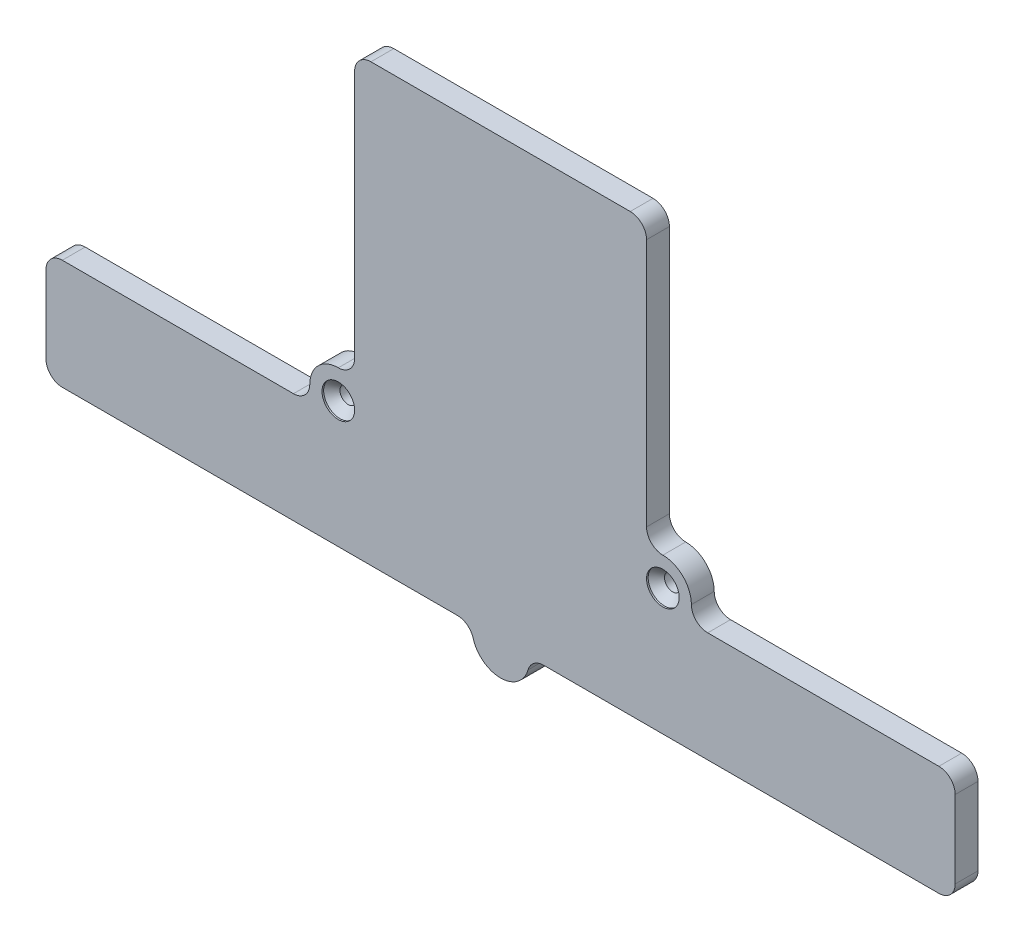
SolidWorks part; units mm, degrees
ref_plane "Front Plane" through (0, 0, 0) normal (0, 0, 1) x (1, 0, 0)
ref_plane "Top Plane" through (0, 0, 0) normal (0, 1, 0) x (1, 0, 0)
ref_plane "Right Plane" through (0, 0, 0) normal (1, 0, 0) x (0, 0, -1)
sketch "Sketch1" plane through (0, 0, 0) normal (0, 0, 1) x (1, 0, 0)
  line L8 (-53.75, -26.75) -> (-5.2915, -26.75)
  line L9 (55.75, -24.75) -> (55.75, -15.25)
  line L10 (53.75, -13.25) -> (25.4, -13.25)
  line L11 (17.9, -5.75) -> (17.9, 24.75)
  line L12 (15.9, 26.75) -> (-15.9, 26.75)
  line L13 (-17.9, 24.75) -> (-17.9, -5.75)
  line L14 (-25.4, -13.25) -> (-53.75, -13.25)
  line L15 (-55.75, -15.25) -> (-55.75, -24.75)
  line L16 (-53.75, -26.75) -> (-5.2915, -26.75)
  line L17 (55.75, -24.75) -> (55.75, -15.25)
  line L18 (53.75, -13.25) -> (25.4, -13.25)
  line L19 (17.9, -5.75) -> (17.9, 24.75)
  line L20 (15.9, 26.75) -> (-15.9, 26.75)
  line L21 (-17.9, 24.75) -> (-17.9, -5.75)
  line L22 (-25.4, -13.25) -> (-53.75, -13.25)
  line L23 (-55.75, -15.25) -> (-55.75, -24.75)
  line L66 (5.2915, -26.75) -> (53.75, -26.75)
  line L67 (5.2915, -26.75) -> (53.75, -26.75)
  arc A12 (53.75, -26.75) -> (55.75, -24.75) centre (53.75, -24.75) ccw
  arc A13 (55.75, -15.25) -> (53.75, -13.25) centre (53.75, -15.25) ccw
  arc A14 (23.4, -11.25) -> (25.4, -13.25) centre (25.4, -11.25) ccw
  arc A15 (23.4, -11.25) -> (19.9, -7.75) centre (19.9, -11.25) ccw
  arc A16 (17.9, -5.75) -> (19.9, -7.75) centre (19.9, -5.75) ccw
  arc A17 (17.9, 24.75) -> (15.9, 26.75) centre (15.9, 24.75) ccw
  arc A18 (-15.9, 26.75) -> (-17.9, 24.75) centre (-15.9, 24.75) ccw
  arc A19 (-19.9, -7.75) -> (-17.9, -5.75) centre (-19.9, -5.75) ccw
  arc A20 (-19.9, -7.75) -> (-23.4, -11.25) centre (-19.9, -11.25) ccw
  arc A21 (-25.4, -13.25) -> (-23.4, -11.25) centre (-25.4, -11.25) ccw
  arc A22 (-53.75, -13.25) -> (-55.75, -15.25) centre (-53.75, -15.25) ccw
  arc A23 (-55.75, -24.75) -> (-53.75, -26.75) centre (-53.75, -24.75) ccw
  arc A24 (53.75, -26.75) -> (55.75, -24.75) centre (53.75, -24.75) ccw
  arc A25 (55.75, -15.25) -> (53.75, -13.25) centre (53.75, -15.25) ccw
  arc A26 (23.4, -11.25) -> (25.4, -13.25) centre (25.4, -11.25) ccw
  arc A27 (23.4, -11.25) -> (19.9, -7.75) centre (19.9, -11.25) ccw
  arc A28 (17.9, -5.75) -> (19.9, -7.75) centre (19.9, -5.75) ccw
  arc A29 (17.9, 24.75) -> (15.9, 26.75) centre (15.9, 24.75) ccw
  arc A30 (-15.9, 26.75) -> (-17.9, 24.75) centre (-15.9, 24.75) ccw
  arc A31 (-19.9, -7.75) -> (-17.9, -5.75) centre (-19.9, -5.75) ccw
  arc A32 (-19.9, -7.75) -> (-23.4, -11.25) centre (-19.9, -11.25) ccw
  arc A33 (-25.4, -13.25) -> (-23.4, -11.25) centre (-25.4, -11.25) ccw
  arc A34 (-53.75, -13.25) -> (-55.75, -15.25) centre (-53.75, -15.25) ccw
  arc A35 (-55.75, -24.75) -> (-53.75, -26.75) centre (-53.75, -24.75) ccw
  arc A100 (-3.3673, -28.2045) -> (-5.2915, -26.75) centre (-5.2915, -28.75) ccw
  arc A101 (-3.3673, -28.2045) -> (-5.2915, -26.75) centre (-5.2915, -28.75) ccw
  arc A102 (-3.3673, -28.2045) -> (3.3673, -28.2045) centre (0, -27.25) ccw
  arc A103 (-3.3673, -28.2045) -> (3.3673, -28.2045) centre (0, -27.25) ccw
  arc A104 (5.2915, -26.75) -> (3.3673, -28.2045) centre (5.2915, -28.75) ccw
  arc A105 (5.2915, -26.75) -> (3.3673, -28.2045) centre (5.2915, -28.75) ccw
  dimension "D1" = 0
extrude "Boss-Extrude1" add sketch "Sketch1" along normal blind 2.8
sketch "Sketch3" plane through (0, 0, 2.8) normal (0, 0, 1) x (1, 0, 0)
  line L0 (0, 32.8811) -> (0, -41.8665) construction
  circle A0 centre (-19.9, -11.25) radius 1
  arc A1 (-19.9, -7.75) -> (-23.4, -11.25) centre (-19.9, -11.25) ccw construction
  circle A2 centre (19.9, -11.25) radius 1
  dimension "D1" = 2
extrude "Cut-Extrude1" cut sketch "Sketch3" against normal up to next
hole_wizard "CSK for M2 Flat Head Machine Screw1" positions "Sketch5" profile "Sketch4" countersink size "M2" standard "ANSI Metric" end condition through all
sketch "Sketch5" plane through (0, 0, 2.8) normal (0, 0, 1) x (1, 0, 0)
  point P0 (-19.9, -11.25)
  point P3 (19.9, -11.25)
sketch "Sketch4" plane through (-19.9, -11.25, 2.8) normal (1, 0, 0) x (0, -1, 0)
  line L0 (0, 0) -> (0, 2.8)
  line L1 (0, 2.8) -> (1, 2.8)
  line L2 (1, 2.8) -> (1, 1.2)
  line L3 (1, 1.2) -> (2, 0.2)
  line L4 (2, 0.2) -> (2, 0)
  line L6 (2, 0) -> (0, 0)
  line L7 (-1, 1.2) -> (-2, 0.2) construction
  line L11 (0, -6.35) -> (0, 107.95) construction
  dimension "Thru Hole Dia." = 2
  dimension "Thru Hole Depth" = 2.8
  dimension "C'Sink Dia." = 4
  dimension "C'Sink Angle" = 90
  dimension "Head Clearance" = 0.2
ref_plane "Plane1" through (0, 0, 2.8) normal (0, 0, 1) x (1, 0, 0)
sketch "Sketch6" plane through (0, 0, 2.8) normal (0, 0, 1) x (1, 0, 0)
  line L0 (0, -30.75) -> (55.75, -30.75) construction
  line L1 (55.75, -30.75) -> (55.75, -24.75) construction
  arc A0 (-3.3673, -28.2045) -> (3.3673, -28.2045) centre (0, -27.25) ccw construction
  point P8 (55.75, -30.75)
